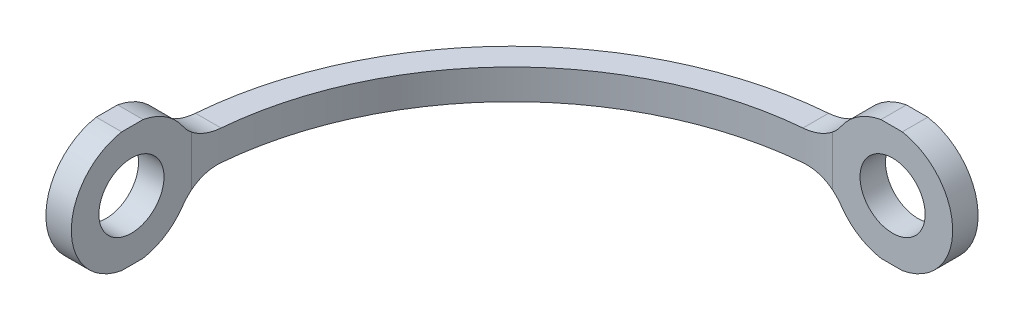
SolidWorks part; units mm, degrees
ref_plane "Front Plane" through (0, 0, 0) normal (0, 0, 1) x (1, 0, 0)
ref_plane "Top Plane" through (0, 0, 0) normal (0, 1, 0) x (1, 0, 0)
ref_plane "Right Plane" through (0, 0, 0) normal (1, 0, 0) x (0, 0, -1)
sketch "Sketch1" plane through (0, 0, 0) normal (0, 1, 0) x (1, 0, 0)
  line L0 (-24.5437, 0) -> (0, 0) construction
  line L1 (-3.75, 23.75) -> (3.75, 23.75)
  line L2 (-3.75, 23.75) -> (-3.75, 25.3375)
  line L3 (-3.75, 25.3375) -> (3.75, 25.3375)
  line L4 (3.75, 23.75) -> (3.75, 25.3375)
  line L5 (-3.75, 23.75) -> (3.75, 25.3375) construction
  line L6 (-3.75, 25.3375) -> (3.75, 23.75) construction
  line L7 (-25.3375, 3.75) -> (-23.75, 3.75)
  line L8 (-25.3375, 3.75) -> (-25.3375, -3.75)
  line L9 (-25.3375, -3.75) -> (-23.75, -3.75)
  line L10 (-23.75, 3.75) -> (-23.75, -3.75)
  line L11 (-25.3375, 3.75) -> (-23.75, -3.75) construction
  line L12 (-25.3375, -3.75) -> (-23.75, 3.75) construction
  line L13 (0, 0) -> (0, 24.5437) construction
  arc A0 (-23.75, 3.75) -> (-3.75, 23.75) centre (-3.75, 3.75) cw
  arc A1 (-25.3375, 3.75) -> (-3.75, 25.3375) centre (-3.75, 3.75) cw
  point P0 (0, 24.5437)
  point P5 (-24.5437, 0)
  dimension "D3" = 20
  dimension "D1" = 1.5875
  dimension "D2" = 7.5
extrude "Boss-Extrude1" add sketch "Sketch1" along normal mid plane 7.5 contours L10 L7 L8 L9 | L1 L4 L3 L2 region at (0, 0, -24.5437) region at (-24.5437, 0, 0)
extrude "Boss-Extrude2" add sketch "Sketch1<3>" along normal mid plane 1.875 contours A1 L7 A0 L2 region at (-18.108, 0, -18.108)
sketch "Sketch1<3>" plane through (0, 0, 0) normal (0, 1, 0) x (1, 0, 0) same geometry as "Sketch1"
sketch "Sketch2" plane through (0, 0, -23.75) normal (0, 0, 1) x (1, 0, 0)
  line L0 (3.75, 3.75) -> (3.75, -3.75) construction
  circle A0 centre (0, 0) radius 2.032
  circle A2 centre (-0.0586, 0) radius 3.8086
  point P4 (3.75, 0)
  line M3 (3.75, -3.75) -> (3.75, 3.75)
  line M6 (-3.75, -3.75) -> (3.75, -3.75)
  line M7 (3.75, 3.75) -> (-3.75, 3.75)
  line M8 (-3.75, 3.75) -> (-3.75, 0.9375)
  line M10 (-3.75, -0.9375) -> (-3.75, -3.75)
  dimension "D1" = 4.064
extrude "Cut-Extrude1" cut sketch "Sketch2" against normal through all contours A0 | M7 M8 | M3 M7 | M6 M3 | M10 M6 region at (0, 0, -23.75) region at (-2.967, 3.0059, -23.75) region at (-2.967, -3.0059, -23.75) region at (2.9557, 2.9023, -23.75) region at (2.9557, -2.9023, -23.75)
sketch "Sketch3" plane through (-23.75, 0, 0) normal (1, 0, 0) x (0, 0, -1)
  circle A0 centre (0, 0) radius 2.032
  circle A1 centre (0.0586, 0) radius 3.8086
  line M1 (-3.75, -3.75) -> (3.75, -3.75)
  line M2 (3.75, -3.75) -> (3.75, -0.9375)
  line M4 (3.75, 0.9375) -> (3.75, 3.75)
  line M5 (3.75, 3.75) -> (-3.75, 3.75)
  line M6 (-3.75, 3.75) -> (-3.75, -3.75)
  dimension "D1" = 4.064
extrude "Cut-Extrude2" cut sketch "Sketch3" against normal through all contours A0 | A1 M6 M1 | A1 M5 M6 | A1 M4 M5 | A1 M1 M2 region at (-23.75, 0, 0) region at (-23.75, 3.0059, -2.967) region at (-23.75, -3.0059, -2.967) region at (-23.75, 2.9023, 2.9557) region at (-23.75, -2.9023, 2.9557)
fillet "Fillet5" radius 2.8125 4 edges at (-3.75, -0.9375, -24.5437) (-3.75, 0.9375, -24.5437) (-24.5437, -0.9375, -3.75) (-24.5437, 0.9375, -3.75)
